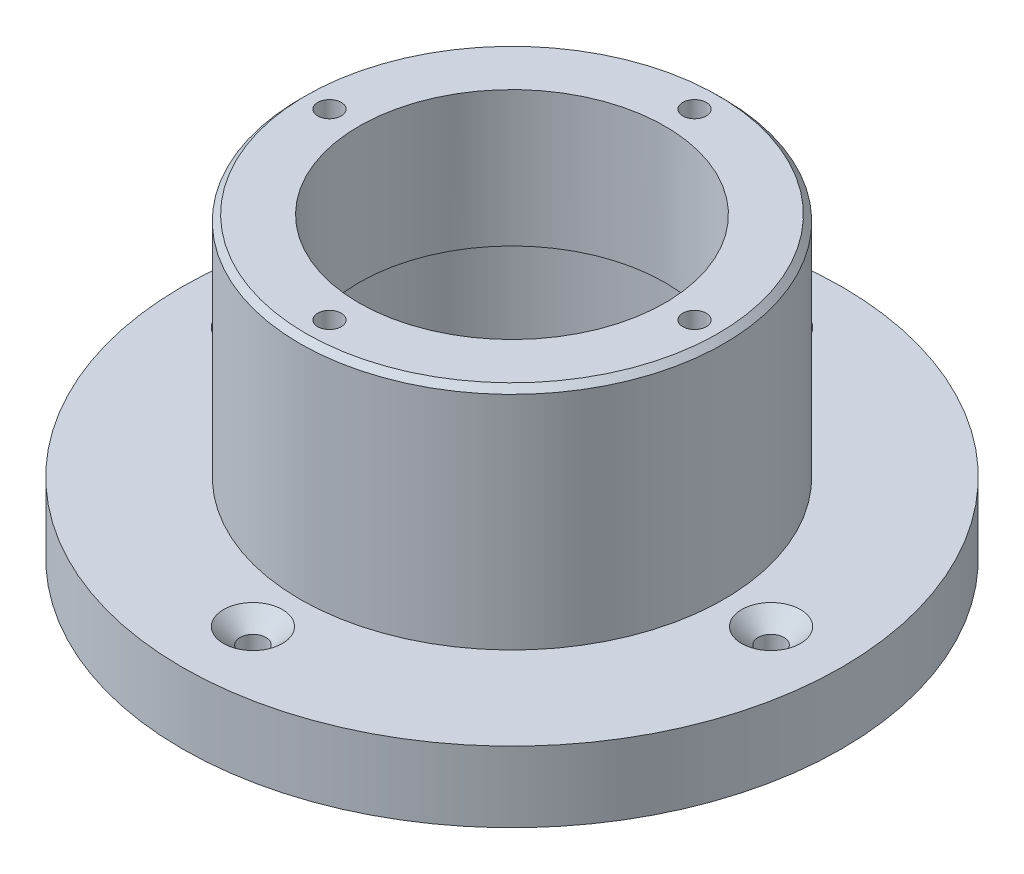
SolidWorks part; units mm, degrees
material "ABS"
ref_plane "Спереди" through (0, 0, 0) normal (0, 0, 1) x (1, 0, 0)
ref_plane "Сверху" through (0, 0, 0) normal (0, 1, 0) x (1, 0, 0)
ref_plane "Справа" through (0, 0, 0) normal (1, 0, 0) x (0, 0, -1)
sketch "Эскиз1" plane through (0, 0, 0) normal (0, 1, 0) x (1, 0, 0)
  circle A0 centre (0, 0) radius 26
  dimension "D1" = 52
extrude "Бобышка-Вытянуть1" add sketch "Эскиз1" along normal blind 4
sketch "Эскиз2" plane through (0, 4, 0) normal (0, 1, 0) x (1, 0, 0)
  circle A0 centre (0, 0) radius 18
  dimension "D1" = 36
extrude "Бобышка-Вытянуть2" add sketch "Эскиз2" along normal blind 19.3
sketch "Эскиз3" plane through (0, 23.3, 0) normal (0, 1, 0) x (1, 0, 0)
  circle A0 centre (0, 0) radius 13
  dimension "D1" = 26
extrude "Вырез-Вытянуть1" cut sketch "Эскиз3" along direction (0, 1, 0) on the side against the normal offset from surface (10.3 mm away) 13 up to face at (0, 0, 26)
sketch "Эскиз4" plane through (0, 4, 0) normal (0, 1, 0) x (1, 0, 0)
  circle A0 centre (0, 0) radius 22 construction
  circle A1 centre (-22, 0) radius 2.2
  circle A2 centre (0, 22) radius 2.2
  circle A3 centre (22, 0) radius 2.2
  circle A4 centre (0, -22) radius 2.2
  point P14 (0, 0)
  dimension "D1" = 44
  dimension "D2" = 4.4
  dimension "D3" = 4
sketch "Эскиз6" plane through (0, 13, 0) normal (0, 1, 0) x (1, 0, 0)
  circle A0 centre (0, 0) radius 13
  dimension "D1" = 26
extrude "Вырез-Вытянуть4" cut sketch "Эскиз6" against normal through all
sketch "Эскиз7" plane through (0, 23.3, 0) normal (0, 1, 0) x (1, 0, 0)
  circle A0 centre (0, 0) radius 15.5 construction
  circle A1 centre (-15.5, 0) radius 1
  circle A2 centre (0, 15.5) radius 1
  circle A3 centre (15.5, 0) radius 1
  circle A4 centre (0, -15.5) radius 1
  point P14 (0, 0)
  dimension "D1" = 31
  dimension "D2" = 2
extrude "Вырез-Вытянуть5" cut sketch "Эскиз7" against normal blind 5
sketch "Эскиз8" plane through (0, 4, 0) normal (0, 1, 0) x (1, 0, 0)
  circle A0 centre (0, 0) radius 26
  circle A1 centre (0, 0) radius 28
  dimension "D1" = 56
  dimension "D2" = 52
extrude "Бобышка-Вытянуть3" add sketch "Эскиз8" against normal blind 6
chamfer "Фаска1" distance 0.5 angle 45 1 edges at (0, -2, 26)
chamfer "Фаска2" distance 0.5 angle 45 1 edges at (0, 23.3, 18)
ref_axis "Ось1" through (0, -20.7688, 22) along (0, 1, 0)
sketch "Эскиз9" plane through (0, 0, 0) normal (1, 0, 0) x (0, 0, -1)
  line L1 (-22, -20.7688) -> (-22, 30.1347) construction
  line L2 (-20.9, 2.648) -> (-19.5, 4)
  line L3 (22, 4) -> (-22, 4) construction
  line L4 (-19.5, 4) -> (-22, 4)
  line L5 (-19.8, 4) -> (-24.2, 4) construction
  line L6 (-22, 2.648) -> (-22, 4)
  line L7 (-20.9, 2.648) -> (-20.9, -2)
  line L8 (-28, -2) -> (28, -2) construction
  line L9 (-20.9, -2) -> (-22, -2)
  line L10 (-22, -2) -> (-22, 2.648)
  dimension "D1" = 1.1
  dimension "D2" = 2.5
  dimension "D3" = 46
revolve "Вырез-Повернуть2" cut sketch "Эскиз9" angle 360 about axis through (0, -20.7688, 22) along (0, 1, 0)
pattern_circular "Круговой массив1" count 4 over 360 about axis through (0, 23.3, 0) along (0, -1, 0) of "Вырез-Повернуть2"
sketch "Эскиз10" plane through (0, 0, 0) normal (0, -1, 0) x (1, 0, 0)
  circle A0 centre (0, 0) radius 14
  dimension "D1" = 28
extrude "Вырез-Вытянуть7" cut sketch "Эскиз10" against normal blind 11.8 contours A0
